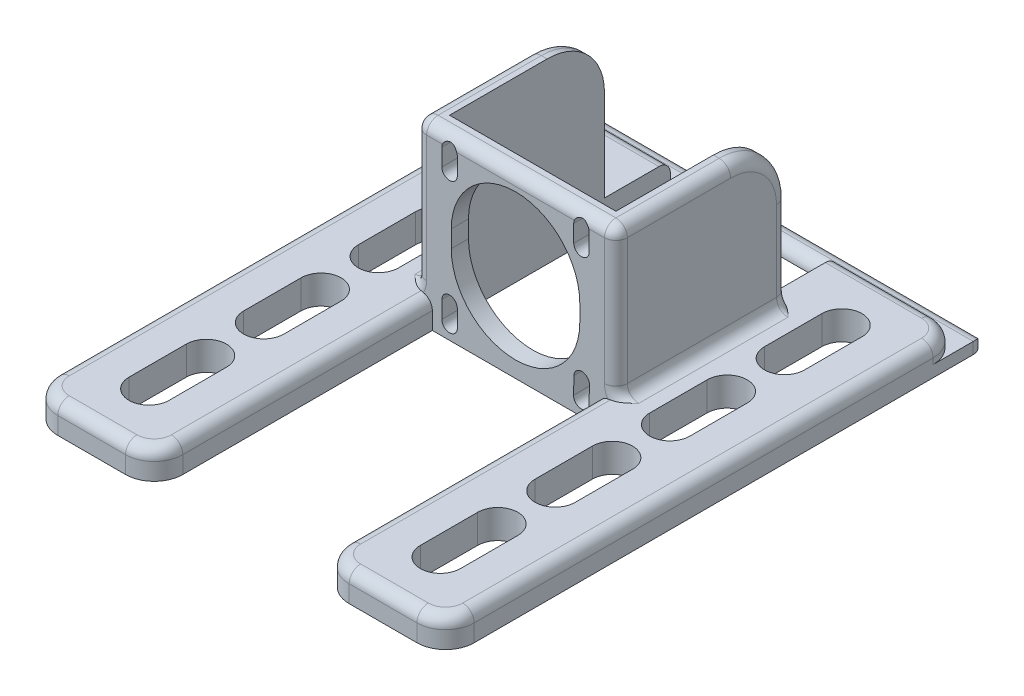
SolidWorks part; units mm, degrees
material "Grey Pro"
ref_plane "Front Plane" through (0, 0, 0) normal (0, 0, 1) x (1, 0, 0)
ref_plane "Top Plane" through (0, 0, 0) normal (0, 1, 0) x (1, 0, 0)
ref_plane "Right Plane" through (0, 0, 0) normal (1, 0, 0) x (0, 0, -1)
sketch "Sketch6" plane through (0, 0, 0) normal (0, 0, 1) x (1, 0, 0)
  line L0 (14.5, -14.5) -> (-14.5, -14.5) construction
  line L1 (14.5, 14.5) -> (14.5, -14.5)
  line L2 (-14.5, 14.5) -> (14.5, 14.5) construction
  line L3 (-14.5, -14.5) -> (-14.5, 14.5)
  line L4 (-14.15, 14.5) -> (-14.15, -14.5) construction
  line L5 (14.15, 14.5) -> (14.15, -14.5)
  line L6 (-14.15, 0) -> (14.15, 0) construction
  line L7 (-11.5, -10) -> (-11.5, -13) construction
  line L8 (-11.5, 11.5) -> (11.5, -11.5) construction
  line L9 (11.5, 11.5) -> (-11.5, -11.5) construction
  line L10 (-10.15, -10) -> (-10.15, -13)
  line L11 (-12.85, -10) -> (-12.85, -13)
  line L12 (11.5378, -10.0005) -> (11.4622, -12.9995) construction
  line L13 (10.1882, -9.9664) -> (10.1126, -12.9655)
  line L14 (12.8874, -10.0345) -> (12.8118, -13.0336)
  line L15 (-11.5, 10) -> (-11.5, 13) construction
  line L16 (-10.15, 10) -> (-10.15, 13)
  line L17 (-12.85, 10) -> (-12.85, 13)
  line L18 (11.5, 10) -> (11.5, 13) construction
  line L19 (10.15, 10) -> (10.15, 13)
  line L20 (12.85, 10) -> (12.85, 13)
  line L21 (0, -1.5) -> (0, 1.5) construction
  line L22 (-11.2, -1.5) -> (-11.2, 1.5)
  line L23 (11.2, -1.5) -> (11.2, 1.5)
  line L24 (14.5, -14.5) -> (14.5, -15.5)
  line L26 (-14.5, 14.5) -> (-14.5, 15.5)
  line L27 (-14.5, 15.5) -> (14.5, 15.5)
  line L28 (14.5, 14.5) -> (14.5, 15.5)
  line L29 (-14.5, -15.5) -> (14.5, -15.5)
  line L30 (-14.5, -14.5) -> (-14.5, -15.5)
  circle A0 centre (-11.5, -11.5) radius 1.25 construction
  circle A1 centre (11.5, -11.5) radius 1.25 construction
  circle A2 centre (-11.5, 11.5) radius 1.25 construction
  circle A3 centre (11.5, 11.5) radius 1.25 construction
  arc A4 (-10.15, -10) -> (-12.85, -10) centre (-11.5, -10) ccw
  arc A5 (-12.85, -13) -> (-10.15, -13) centre (-11.5, -13) ccw
  arc A6 (10.1882, -9.9664) -> (12.8874, -10.0345) centre (11.5378, -10.0005) cw
  arc A7 (12.8118, -13.0336) -> (10.1126, -12.9655) centre (11.4622, -12.9995) cw
  arc A8 (-10.15, 10) -> (-12.85, 10) centre (-11.5, 10) cw
  arc A9 (-12.85, 13) -> (-10.15, 13) centre (-11.5, 13) cw
  arc A10 (10.15, 10) -> (12.85, 10) centre (11.5, 10) ccw
  arc A11 (12.85, 13) -> (10.15, 13) centre (11.5, 13) ccw
  arc A12 (-11.2, -1.5) -> (11.2, -1.5) centre (0, -1.5) ccw
  arc A13 (11.2, 1.5) -> (-11.2, 1.5) centre (0, 1.5) ccw
  point P10 (0, 0)
  point P11 (0, 14.5)
  point P24 (-11.5, -11.5)
  point P32 (11.5, -11.5)
  point P38 (-11.5, 11.5)
  point P45 (11.5, 11.5)
  point P50 (0, 0)
  point P55 (0, 0)
  point P58 (-14.5, 15)
  point P61 (-14.5, -15)
  dimension "D2" = 2.5
  dimension "D13" = 2.5
  dimension "D1" = 28.3
  dimension "D3" = 23
  dimension "D4" = 23
  dimension "D5" = 1.5
  dimension "D6" = 22.4
  dimension "D7" = 29
  dimension "D8" = 0.35
  dimension "D9" = 3
  dimension "D10" = 1
  dimension "D11" = 3
  dimension "D12" = 2.7
  dimension "D14" = 1.5
  dimension "D15" = 1.5
  dimension "D16" = 1.5005
extrude "Boss-Extrude1" add sketch "Sketch6" along normal blind 3
sketch "Sketch8" plane through (14.5, 0, 0) normal (1, 0, 0) x (0, 0, -1)
  line L1 (-41.5, -10.5) -> (38.5, -10.5)
  line L2 (-41.5, -10.5) -> (-41.5, -15.5)
  line L3 (-41.5, -15.5) -> (38.5, -15.5)
  line L4 (38.5, -10.5) -> (38.5, -15.5)
  line L6 (0, 15.5) -> (0, -15.5) construction
  line L7 (-3, -15.5) -> (0, -15.5) construction
  dimension "D1" = 5
  dimension "D2" = 80
  dimension "D3" = 38.5
extrude "Boss-Extrude3" add sketch "Sketch8" along normal blind 21.8
sketch "Sketch9" plane through (0, -10.5, 0) normal (0, 1, 0) x (1, 0, 0)
  line L0 (-14.5, 0) -> (14.5, 0) construction
  line L1 (36.3, 38.5) -> (14.5, 38.5) construction
  line L2 (21.9, 28.5) -> (21.9, 18.5)
  line L3 (36.3, -41.5) -> (14.5, -41.5) construction
  line L4 (28.9, 28.5) -> (28.9, 18.5)
  line L5 (28.9, -11.5) -> (28.9, -21.5)
  line L6 (28.9, -21.5) -> (28.9, -31.5) construction
  line L7 (21.9, -11.5) -> (21.9, -21.5)
  line L8 (21.9, -21.5) -> (21.9, -31.5) construction
  line L9 (28.9, -1.5) -> (28.9, -11.5) construction
  line L10 (21.9, -1.5) -> (21.9, -11.5) construction
  line L11 (21.9, 18.5) -> (21.9, 8.5) construction
  line L12 (21.9, 8.5) -> (21.9, -1.5)
  line L13 (28.9, 18.5) -> (28.9, 8.5) construction
  line L14 (28.9, 8.5) -> (28.9, -1.5)
  arc A0 (28.9, 28.5) -> (21.9, 28.5) centre (25.4, 28.5) ccw
  arc A1 (21.9, 18.5) -> (28.9, 18.5) centre (25.4, 18.5) ccw
  arc A2 (28.9, 8.5) -> (21.9, 8.5) centre (25.4, 8.5) ccw
  arc A3 (21.9, -1.5) -> (28.9, -1.5) centre (25.4, -1.5) ccw
  arc A4 (28.9, -11.5) -> (21.9, -11.5) centre (25.4, -11.5) ccw
  arc A5 (28.9, -21.5) -> (21.9, -21.5) centre (25.4, -21.5) ccw construction
  arc A6 (21.9, -31.5) -> (28.9, -31.5) centre (25.4, -31.5) ccw construction
  arc A7 (21.9, -21.5) -> (28.9, -21.5) centre (25.4, -21.5) ccw
  arc A8 (28.9, -31.5) -> (21.9, -31.5) centre (25.4, -31.5) ccw construction
  arc A9 (21.9, 8.5) -> (28.9, 8.5) centre (25.4, 8.5) ccw construction
  arc A10 (28.9, -1.5) -> (21.9, -1.5) centre (25.4, -1.5) ccw construction
  arc A11 (21.9, 28.5) -> (28.9, 28.5) centre (25.4, 28.5) ccw construction
  arc A12 (28.9, 18.5) -> (21.9, 18.5) centre (25.4, 18.5) ccw construction
  arc A13 (21.9, -11.5) -> (28.9, -11.5) centre (25.4, -11.5) ccw construction
  point P4 (0, 0)
  dimension "D1" = 7
  dimension "D2" = 25.4
  dimension "D3" = 10
  dimension "D5" = 10
  dimension "D4" = 7
extrude "Cut-Extrude1" cut sketch "Sketch9" against normal up to surface (5 mm away) up to face at (12.7, -15.5, 1.5)
sketch "Sketch13" plane through (0, 0, 41.5) normal (0, 0, 1) x (1, 0, 0)
  line L5 (36.3, -15.5) -> (14.5, -15.5)
  line L6 (36.3, -15.5) -> (36.3, -10.5)
  line L7 (36.3, -10.5) -> (14.5, -10.5)
  line L8 (14.5, -15.5) -> (14.5, -10.5)
extrude "Boss-Extrude6" add sketch "Sketch13" along normal blind 10
sketch "Sketch14" plane through (0, -10.5, 0) normal (0, 1, 0) x (1, 0, 0)
  line L0 (21.9, -31.5) -> (21.9, -41.5)
  line L1 (28.9, -31.5) -> (28.9, -41.5)
  line L2 (36.3, 38.5) -> (36.3, -51.5) construction
  line L3 (28.9, -21.5) -> (28.9, -11.5) construction
  arc A0 (28.9, -31.5) -> (21.9, -31.5) centre (25.4, -31.5) ccw
  arc A1 (21.9, -41.5) -> (28.9, -41.5) centre (25.4, -41.5) ccw
  arc A3 (21.9, -21.5) -> (28.9, -21.5) centre (25.4, -21.5) ccw construction
  arc A4 (28.9, -11.5) -> (21.9, -11.5) centre (25.4, -11.5) ccw construction
  arc A5 (21.9, -1.5) -> (28.9, -1.5) centre (25.4, -1.5) ccw construction
  arc A6 (28.9, 8.5) -> (21.9, 8.5) centre (25.4, 8.5) ccw construction
  arc A7 (21.9, -31.5) -> (28.9, -31.5) centre (25.4, -31.5) ccw construction
  arc A8 (28.9, -41.5) -> (21.9, -41.5) centre (25.4, -41.5) ccw construction
  dimension "D1" = 10
  dimension "D2" = 10
  dimension "D3" = 10
  dimension "D4" = 10
extrude "Cut-Extrude2" cut sketch "Sketch14" against normal up to surface (5 mm away) up to face at (25.4, -15.5, -23.5)
mirror "Mirror1" about plane through (0, 0, 0) normal (1, 0, 0) of "Cut-Extrude2", "Cut-Extrude1", "Boss-Extrude3", "Boss-Extrude6"
sketch "Sketch12" plane through (0, 0, 3) normal (0, 0, 1) x (1, 0, 0)
  line L0 (0, -15.5) -> (0, 15.5) construction
  line L1 (14.5, 15.5) -> (17.5, 15.5)
  line L2 (14.5, 15.5) -> (14.5, -10.5)
  line L3 (14.5, -10.5) -> (17.5, -10.5)
  line L4 (17.5, 15.5) -> (17.5, -10.5)
  line L5 (-14.5, -15.5) -> (14.5, -15.5) construction
  line L6 (-14.5, 15.5) -> (14.5, 15.5) construction
  line L7 (-14.5, -10.5) -> (-17.5, -10.5)
  line L8 (-17.5, 15.5) -> (-17.5, -10.5)
  line L9 (-14.5, 15.5) -> (-17.5, 15.5)
  line L10 (-14.5, 15.5) -> (-14.5, -10.5)
  dimension "D1" = 3
extrude "Boss-Extrude5" add sketch "Sketch12" against normal blind 30
fillet "Fillet6" radius 5 6 edges at (36.3, -13, 51.5) (14.5, -13, 51.5) (-36.3, -13, -38.5) (-36.3, -13, 51.5) (-14.5, -13, 51.5) (36.3, -13, -38.5)
fillet "Fillet7" radius 2 2 edges at (-17.5, -10.5, -12) (17.5, -10.5, -12)
fillet "Fillet9" radius 10 2 edges at (-16, 15.5, -27) (16, 15.5, -27)
fillet "Fillet10" radius 2 13 edges at (-18.0858, -9.9142, 3) (18.0858, -9.9142, 3) (-18.0858, -9.9142, -27) (-17.5, -1.5, -27) (-17.5, 12.5711, -24.0711) (18.0858, -9.9142, -27) (17.5, -1.5, -27) (17.5, 12.5711, -24.0711) (-17.5, 3.5, 3) (0, 15.5, 3) (17.5, 3.5, 3) (-17.5, 15.5, -7) (17.5, 15.5, -7)
fillet "Fillet11" radius 2 15 edges at (15.2679, -10.5, 3) (-22.9, -10.5, -38.5) (-36.3, -10.5, 6.5) (-25.4, -10.5, 51.5) (-15.9645, -10.5, 50.0355) (-34.8355, -10.5, 50.0355) (-34.8355, -10.5, -37.0355) (36.3, -10.5, 6.5) (25.4, -10.5, 51.5) (22.9, -10.5, -38.5) (34.8355, -10.5, 50.0355) (15.9645, -10.5, 50.0355) (34.8355, -10.5, -37.0355) (-15.2679, -10.5, 3) (-17.0359, -10.5, 2.8213)
sketch "Sketch17" plane through (0, -15.5, 0) normal (0, -1, 0) x (1, 0, 0)
  line L2 (-36.3, -33.5) -> (-36.3, -42.5)
  line L3 (-36.3, -42.5) -> (36.3, -42.5)
  line L4 (36.3, -42.5) -> (36.3, -33.5)
  line L5 (-31.3, -38.5) -> (31.3, -38.5)
  arc A4 (31.3, -38.5) -> (36.3, -33.5) centre (31.3, -33.5) ccw construction
  arc A5 (-36.3, -33.5) -> (-31.3, -38.5) centre (-31.3, -33.5) ccw construction
  arc A6 (31.3, -38.5) -> (36.3, -33.5) centre (31.3, -33.5) ccw
  arc A7 (-36.3, -33.5) -> (-31.3, -38.5) centre (-31.3, -33.5) ccw
  dimension "D1" = 4
extrude "Boss-Extrude10" add sketch "Sketch17" against normal blind 2
fillet "Fillet13" radius 2 4 edges at (0, -13.5, -38.5) (-36.3, -14.5, -42.5) (36.3, -14.5, -42.5) (0, -13.5, -42.5)
